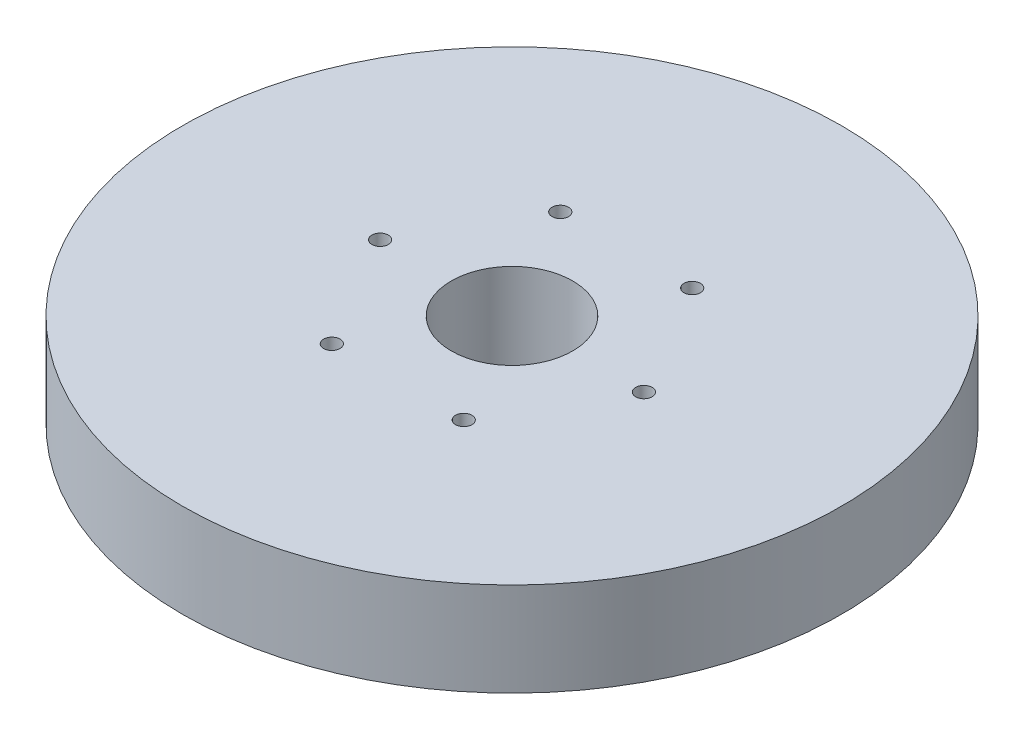
SolidWorks part; units mm, degrees
ref_plane "Front Plane" through (0, 0, 0) normal (0, 0, 1) x (1, 0, 0)
ref_plane "Top Plane" through (0, 0, 0) normal (0, 1, 0) x (1, 0, 0)
ref_plane "Right Plane" through (0, 0, 0) normal (1, 0, 0) x (0, 0, -1)
sketch "Sketch1" plane through (0, 0, 0) normal (0, 1, 0) x (1, 0, 0)
  circle A0 centre (0, 0) radius 95
  dimension "FLANGE_OD" = 190
extrude "Boss-Extrude1" add sketch "Sketch1" along normal blind 27
sketch "Sketch2" plane through (0, 0, 0) normal (0, 1, 0) x (1, 0, 0)
  circle A0 centre (0, 0) radius 17.5
  dimension "BORE_D" = 35
extrude "Cut-Extrude1" cut sketch "Sketch2" along normal through all
sketch "Sketch3" plane through (0, 27, 0) normal (0, 1, 0) x (1, 0, 0)
  circle A0 centre (0, 0) radius 38.0239 construction
  circle A1 centre (-38.0239, 0) radius 2.3685
  dimension "BOLT_D" = 4.737
  dimension "BOLT_PCD" = 76.0478
extrude "Cut-Extrude2" cut sketch "Sketch3" against normal blind 16.7959
pattern_circular "CirPattern1" count 6 over 360 about axis through (0, 0, 0) along (0, 1, 0) of "Cut-Extrude2"
